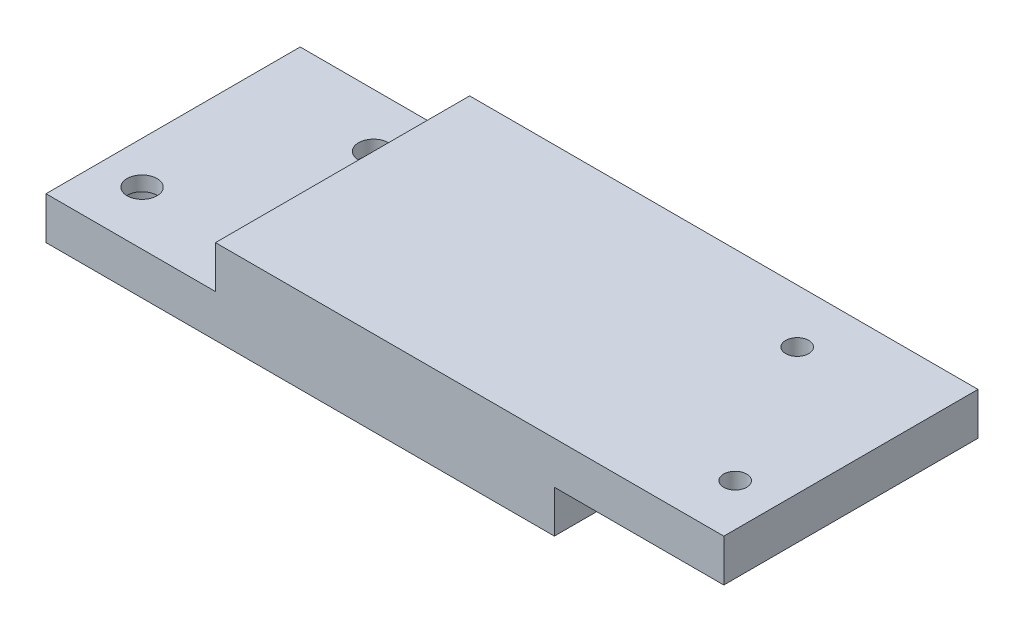
SolidWorks part; units mm, degrees
ref_plane "Front Plane" through (0, 0, 0) normal (0, 0, 1) x (1, 0, 0)
ref_plane "Top Plane" through (0, 0, 0) normal (0, 1, 0) x (1, 0, 0)
ref_plane "Right Plane" through (0, 0, 0) normal (1, 0, 0) x (0, 0, -1)
sketch "Sketch1" plane through (0, 0, 0) normal (0, 1, 0) x (1, 0, 0)
  line L0 (-31.75, 10.9985) -> (31.75, 10.9985) construction
  line L1 (-50.8, 19.05) -> (50.8, 19.05)
  line L2 (-50.8, 19.05) -> (-50.8, -19.05)
  line L3 (-50.8, -19.05) -> (50.8, -19.05)
  line L4 (50.8, 19.05) -> (50.8, -19.05)
  line L5 (-50.8, 19.05) -> (-25.4, 19.05)
  line L6 (-50.8, 19.05) -> (-50.8, -19.05)
  line L7 (-50.8, -19.05) -> (-25.4, -19.05)
  line L8 (-25.4, 19.05) -> (-25.4, -19.05)
  line L9 (50.8, 19.05) -> (25.4, 19.05)
  line L10 (50.8, 19.05) -> (50.8, -19.05)
  line L11 (50.8, -19.05) -> (25.4, -19.05)
  line L12 (25.4, 19.05) -> (25.4, -19.05)
  line L13 (31.75, 10.9985) -> (44.45, -10.9985) construction
  line L14 (44.45, -10.9985) -> (-44.45, -10.9985) construction
  line L15 (-44.45, -10.9985) -> (-31.75, 10.9985) construction
  point P4 (0, 19.05)
  point P5 (0, -10.9985)
  point P9 (-50.8, 0)
  point P12 (-31.75, 10.9985)
  point P13 (-44.45, -10.9985)
  point P14 (31.75, 10.9985)
  point P15 (44.45, -10.9985)
  point P20 (38.1, 0)
  dimension "D1" = 101.6
  dimension "D2" = 38.1
  dimension "D3" = 25.4
  dimension "D4" = 25.4
  dimension "D5" = 25.4
  dimension "D6" = 63.5
  dimension "D7" = 25.4
  dimension "D8" = 88.9
extrude "Boss-Extrude1" add sketch "Sketch1" against normal blind 6.35 contours L8 L1 L2 L3 | L12 L1 L8 L3 region at (-38.1, 0, 0) region at (0, 0, 0)
extrude "Boss-Extrude2" add sketch "Sketch1<3>" along normal blind 6.35 contours L12 L1 L8 L3 | L1 L12 L3 L4 region at (0, 0, 0) region at (38.1, 0, 0)
sketch "Sketch1<3>" plane through (0, 0, 0) normal (0, 1, 0) x (1, 0, 0) same geometry as "Sketch1"
hole_wizard "CBORE for #8 Socket Head Cap Screw1" positions "Sketch3" profile "Sketch4" counterbore size "#8" standard "ANSI Inch" end condition up to next
sketch "Sketch3" plane through (0, -6.35, 0) normal (0, -1, 0) x (-1, 0, 0)
  point P0 (31.75, 10.9985)
  point P3 (44.45, -10.9985)
sketch "Sketch4" plane through (-31.75, -6.35, -10.9985) normal (1, 0, 0) x (0, 0, -1)
  line L0 (0, 0) -> (0, 6.35)
  line L1 (0, 6.35) -> (2.2479, 6.35)
  line L3 (2.2479, 6.35) -> (2.2479, 4.1656)
  line L4 (2.2479, 4.1656) -> (3.9687, 4.1656)
  line L5 (3.9687, 4.1656) -> (3.9687, 0)
  line L7 (3.9687, 0) -> (0, 0)
  line L11 (0, -6.35) -> (0, 107.95) construction
  dimension "Thru Hole Dia." = 4.4958
  dimension "Thru Hole Depth" = 6.35
  dimension "C'Bore Dia." = 7.9375
  dimension "C'Bore Depth" = 4.1656
hole_wizard "#8-32 Tapped Hole1" positions "Sketch6" profile "Sketch5" tap size "#8-32" standard "ANSI Inch" end condition through all
sketch "Sketch6" plane through (0, 0, 0) normal (0, -1, 0) x (-1, 0, 0)
  point P1 (-31.75, 10.9985)
  point P9 (-44.45, -10.9985)
cosmetic thread "Hole Thread1" parameters "D2"=4.1656
sketch "Sketch5" plane through (31.75, 0, -10.9985) normal (1, 0, 0) x (0, 0, -1)
  line L0 (0, 0) -> (0, 6.35)
  line L1 (0, 6.35) -> (1.7272, 6.35)
  line L2 (1.7272, 6.35) -> (1.7272, 0)
  line L5 (1.7272, 0) -> (0, 0)
  line L11 (0, -6.35) -> (0, 107.95) construction
  dimension "Thru Tap Drill Dia." = 3.4544
  dimension "Thru Tap Drill Depth" = 6.35
cosmetic thread "Hole Thread2" parameters "D2"=4.1656
